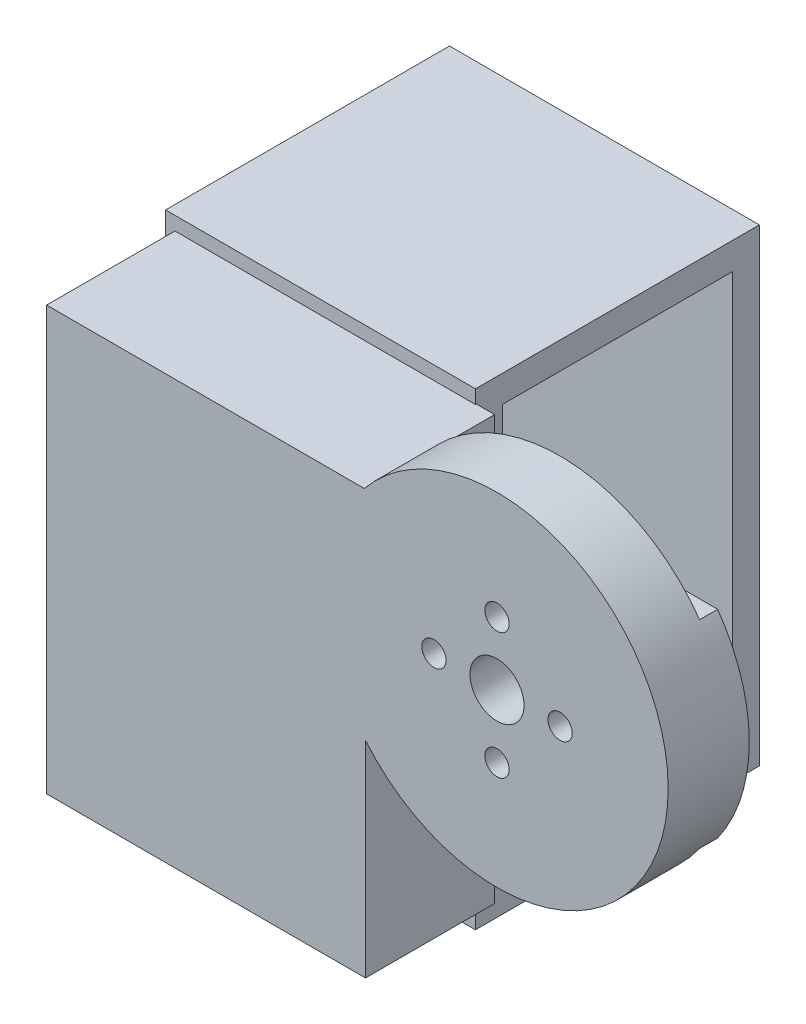
SolidWorks part; units mm, degrees
ref_plane "Front Plane" through (0, 0, 0) normal (0, 0, 1) x (1, 0, 0)
ref_plane "Top Plane" through (0, 0, 0) normal (0, 1, 0) x (1, 0, 0)
ref_plane "Right Plane" through (0, 0, 0) normal (1, 0, 0) x (0, 0, -1)
ref_plane "PZ_p23_000" through (0, 0, 23) normal (0, 0, 1) x (1, 0, 0)
sketch "S_cyl1" plane through (0, 0, 23) normal (0, 0, 1) x (1, 0, 0)
  circle A0 centre (0, 0) radius 19
  dimension "D1_S_cyl1" = 38
extrude "Boss_1" add sketch "S_cyl1" along normal blind 7
ref_plane "PZ_p21_000" through (0, 0, 21) normal (0, 0, 1) x (1, 0, 0)
sketch "S_prism2" plane through (0, 0, 21) normal (0, 0, 1) x (1, 0, 0)
  line L0 (-15.4919, -11) -> (15.4919, -11)
  line L1 (15.4919, 11) -> (-15.4919, 11)
  arc A0 (15.4919, -11) -> (15.4919, 11) centre (0, 0) ccw
  arc A1 (-15.4919, 11) -> (-15.4919, -11) centre (0, 0) ccw
extrude "Boss_2" add sketch "S_prism2" along normal blind 2.1
ref_plane "PZ_p19_600" through (0, 0, 19.6) normal (0, 0, 1) x (1, 0, 0)
sketch "S_box3" plane through (0, 0, 19.6) normal (0, 0, 1) x (1, 0, 0)
  line L0 (-14.5, -5) -> (14, -5)
  line L1 (14, -5) -> (14, 5)
  line L2 (14, 5) -> (-14.5, 5)
  line L3 (-14.5, 5) -> (-14.5, -5)
  dimension "P1" = 14.5
  dimension "P2" = 5
  dimension "P3" = 14
  dimension "P4" = 5
  dimension "P5" = 14
  dimension "P6" = 5
  dimension "P7" = 14.5
  dimension "P8" = 5
extrude "Boss_3" add sketch "S_box3" along normal blind 1.5
ref_plane "PZ_p15_660" through (0, 0, 15.66) normal (0, 0, 1) x (1, 0, 0)
sketch "S_box4" plane through (0, 0, 15.66) normal (0, 0, 1) x (1, 0, 0)
  line L0 (-50, -35) -> (-14.6, -35)
  line L1 (-14.6, -35) -> (-14.6, 12)
  line L2 (-14.6, 12) -> (-50, 12)
  line L3 (-50, 12) -> (-50, -35)
  dimension "P1" = 50
  dimension "P2" = 35
  dimension "P3" = 14.6
  dimension "P4" = 35
  dimension "P5" = 14.6
  dimension "P6" = 12
  dimension "P7" = 50
  dimension "P8" = 12
extrude "Boss_4" add sketch "S_box4" along normal blind 14.34
ref_plane "PZ_m15_760" through (0, 0, -15.76) normal (0, 0, 1) x (1, 0, 0)
sketch "S_box5" plane through (0, 0, -15.76) normal (0, 0, 1) x (1, 0, 0)
  line L0 (-51.035, -38.51) -> (-16.635, -38.51)
  line L1 (-16.635, -38.51) -> (-16.635, -35.51)
  line L2 (-16.635, -35.51) -> (-51.035, -35.51)
  line L3 (-51.035, -35.51) -> (-51.035, -38.51)
  dimension "P1" = 51.035
  dimension "P2" = 38.51
  dimension "P3" = 16.635
  dimension "P4" = 38.51
  dimension "P5" = 16.635
  dimension "P6" = 35.51
  dimension "P7" = 51.035
  dimension "P8" = 35.51
extrude "Boss_5" add sketch "S_box5" along normal blind 31.52
sketch "S_box6" plane through (0, 0, -15.76) normal (0, 0, 1) x (1, 0, 0)
  line L0 (-51.035, 10.51) -> (-16.635, 10.51)
  line L1 (-16.635, 10.51) -> (-16.635, 13.51)
  line L2 (-16.635, 13.51) -> (-51.035, 13.51)
  line L3 (-51.035, 13.51) -> (-51.035, 10.51)
  dimension "P1" = 51.035
  dimension "P2" = 10.51
  dimension "P3" = 16.635
  dimension "P4" = 10.51
  dimension "P5" = 16.635
  dimension "P6" = 13.51
  dimension "P7" = 51.035
  dimension "P8" = 13.51
extrude "Boss_6" add sketch "S_box6" along normal blind 31.52
sketch "S_box7" plane through (0, 0, -15.76) normal (0, 0, 1) x (1, 0, 0)
  line L0 (-51.035, -38.51) -> (-16.635, -38.51)
  line L1 (-16.635, -38.51) -> (-16.635, 13.51)
  line L2 (-16.635, 13.51) -> (-51.035, 13.51)
  line L3 (-51.035, 13.51) -> (-51.035, -38.51)
  dimension "P1" = 51.035
  dimension "P2" = 38.51
  dimension "P3" = 16.635
  dimension "P4" = 38.51
  dimension "P5" = 16.635
  dimension "P6" = 13.51
  dimension "P7" = 51.035
  dimension "P8" = 13.51
extrude "Boss_7" add sketch "S_box7" along normal blind 3
ref_plane "PZ_p12_760" through (0, 0, 12.76) normal (0, 0, 1) x (1, 0, 0)
sketch "S_box8" plane through (0, 0, 12.76) normal (0, 0, 1) x (1, 0, 0)
  line L0 (-51.035, -38.51) -> (-16.635, -38.51)
  line L1 (-16.635, -38.51) -> (-16.635, 13.51)
  line L2 (-16.635, 13.51) -> (-51.035, 13.51)
  line L3 (-51.035, 13.51) -> (-51.035, -38.51)
  dimension "P1" = 51.035
  dimension "P2" = 38.51
  dimension "P3" = 16.635
  dimension "P4" = 38.51
  dimension "P5" = 16.635
  dimension "P6" = 13.51
  dimension "P7" = 51.035
  dimension "P8" = 13.51
extrude "Boss_8" add sketch "S_box8" along normal blind 3
sketch "S_box9" plane through (0, 0, -15.76) normal (0, 0, 1) x (1, 0, 0)
  line L0 (-51.035, -38.51) -> (-48.635, -38.51)
  line L1 (-48.635, -38.51) -> (-48.635, 13.51)
  line L2 (-48.635, 13.51) -> (-51.035, 13.51)
  line L3 (-51.035, 13.51) -> (-51.035, -38.51)
  dimension "P1" = 51.035
  dimension "P2" = 38.51
  dimension "P3" = 48.635
  dimension "P4" = 38.51
  dimension "P5" = 48.635
  dimension "P6" = 13.51
  dimension "P7" = 51.035
  dimension "P8" = 13.51
extrude "Boss_9" add sketch "S_box9" along normal blind 31.52
ref_plane "PX_m51_135" through (-51.135, 0, 0) normal (1, 0, 0) x (0, 0, -1)
sketch "S_hole10" plane through (-51.135, 0, 0) normal (1, 0, 0) x (0, 0, -1)
  circle A0 centre (0, 0) radius 11
  dimension "D1_S_hole10" = 22
extrude "Hole_10" cut sketch "S_hole10" along normal blind 2.6
sketch "S_hole11" plane through (-51.135, 0, 0) normal (1, 0, 0) x (0, 0, -1)
  circle A0 centre (-10.25, -8.3) radius 1.1
  dimension "D1_S_hole11" = 2.2
  dimension "P2" = 10.25
  dimension "P3" = 8.3
extrude "Hole_11" cut sketch "S_hole11" along normal blind 2.6
sketch "S_hole12" plane through (-51.135, 0, 0) normal (1, 0, 0) x (0, 0, -1)
  circle A0 centre (10.25, -32.75) radius 1.1
  dimension "D1_S_hole12" = 2.2
  dimension "P2" = 10.25
  dimension "P3" = 32.75
extrude "Hole_12" cut sketch "S_hole12" along normal blind 2.6
sketch "S_hole13" plane through (-51.135, 0, 0) normal (1, 0, 0) x (0, 0, -1)
  circle A0 centre (-10.25, -32.75) radius 1.1
  dimension "D1_S_hole13" = 2.2
  dimension "P2" = 10.25
  dimension "P3" = 32.75
extrude "Hole_13" cut sketch "S_hole13" along normal blind 2.6
ref_plane "PZ_p19_500" through (0, 0, 19.5) normal (0, 0, 1) x (1, 0, 0)
sketch "S_hole14" plane through (0, 0, 19.5) normal (0, 0, 1) x (1, 0, 0)
  circle A0 centre (0, 0) radius 3
  dimension "D1_S_hole14" = 6
extrude "Hole_14" cut sketch "S_hole14" along normal blind 10.6
sketch "S_hole15" plane through (0, 0, 19.5) normal (0, 0, 1) x (1, 0, 0)
  circle A0 centre (7, 0) radius 1.35
  dimension "D1_S_hole15" = 2.7
  dimension "P2" = 7
extrude "Hole_15" cut sketch "S_hole15" along normal blind 10.6
sketch "S_hole16" plane through (0, 0, 19.5) normal (0, 0, 1) x (1, 0, 0)
  circle A0 centre (0, 7) radius 1.35
  dimension "D1_S_hole16" = 2.7
  dimension "P2" = 7
extrude "Hole_16" cut sketch "S_hole16" along normal blind 10.6
sketch "S_hole17" plane through (0, 0, 19.5) normal (0, 0, 1) x (1, 0, 0)
  circle A0 centre (-7, 0) radius 1.35
  dimension "D1_S_hole17" = 2.7
  dimension "P2" = 7
extrude "Hole_17" cut sketch "S_hole17" along normal blind 10.6
sketch "S_hole18" plane through (0, 0, 19.5) normal (0, 0, 1) x (1, 0, 0)
  circle A0 centre (0, -7) radius 1.35
  dimension "D1_S_hole18" = 2.7
  dimension "P2" = 7
extrude "Hole_18" cut sketch "S_hole18" along normal blind 10.6
sketch "S_hole19" plane through (0, 0, 19.5) normal (0, 0, 1) x (1, 0, 0)
  circle A0 centre (7, 0) radius 2.3
  dimension "D1_S_hole19" = 4.6
  dimension "P2" = 7
extrude "Hole_19" cut sketch "S_hole19" along normal blind 4.5
sketch "S_hole20" plane through (0, 0, 19.5) normal (0, 0, 1) x (1, 0, 0)
  circle A0 centre (0, 7) radius 2.3
  dimension "D1_S_hole20" = 4.6
  dimension "P2" = 7
extrude "Hole_20" cut sketch "S_hole20" along normal blind 4.5
sketch "S_hole21" plane through (0, 0, 19.5) normal (0, 0, 1) x (1, 0, 0)
  circle A0 centre (-7, 0) radius 2.3
  dimension "D1_S_hole21" = 4.6
  dimension "P2" = 7
extrude "Hole_21" cut sketch "S_hole21" along normal blind 4.5
sketch "S_hole22" plane through (0, 0, 19.5) normal (0, 0, 1) x (1, 0, 0)
  circle A0 centre (0, -7) radius 2.3
  dimension "D1_S_hole22" = 4.6
  dimension "P2" = 7
extrude "Hole_22" cut sketch "S_hole22" along normal blind 4.5
equation "\"plate_t\" = 3"
equation "\"clearance\" = 0.4"
